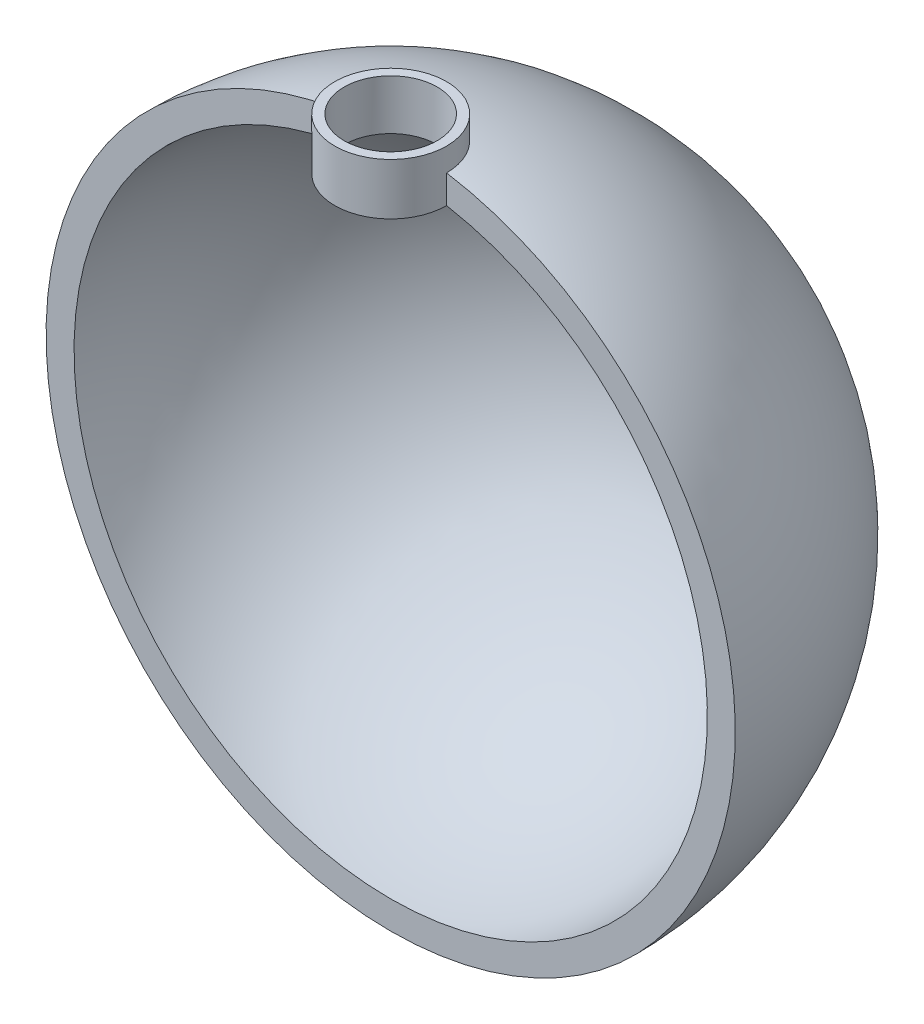
SolidWorks part; units mm, degrees
ref_plane "Front Plane" through (0, 0, 0) normal (0, 0, 1) x (1, 0, 0)
ref_plane "Top Plane" through (0, 0, 0) normal (0, 1, 0) x (1, 0, 0)
ref_plane "Right Plane" through (0, 0, 0) normal (1, 0, 0) x (0, 0, -1)
sketch "Sketch1" plane through (0, 0, 0) normal (0, 0, 1) x (1, 0, 0)
  line L0 (0, 0) -> (0, 185)
  line L1 (0, 185) -> (0, -185)
  arc A0 (0, -170) -> (0, 170) centre (0, 0) ccw
  arc A1 (0, -185) -> (0, 185) centre (0, 0) ccw
revolve "Revolve1" add sketch "Sketch1" angle 180 about L0 region at (4.1367, 177.5, 0)
sketch "Sketch3" plane through (0, 0, 0) normal (0, 1, 0) x (1, 0, 0)
  circle A0 centre (0, 0) radius 30
extrude "Boss-Extrude2" add sketch "Sketch3" along normal blind 195
sketch "Sketch7" plane through (0, 195, 0) normal (0, 1, 0) x (1, 0, 0)
  circle A0 centre (0, 0) radius 25
extrude "Cut-Extrude3" cut sketch "Sketch7" against normal up to surface (195 mm away) up to face at (0, 0, 30)
sketch "Sketch8" plane through (0, 0, 0) normal (0, 0, 1) x (1, 0, 0)
  line L0 (0, 0) -> (0, 170) construction
  line L1 (0, 0) -> (0, 170)
  line L2 (0, 170) -> (0, -170)
  arc A0 (0, -170) -> (0, 170) centre (0, 0) ccw
revolve "Cut-Revolve3" cut sketch "Sketch8" angle 180 about L0 region at (72.1502, 0, 0)
sketch "Sketch10" plane through (0, 0, 0) normal (0, 0, 1) x (1, 0, 0)
  line L0 (0, 0) -> (30, 0)
  line L1 (30, 0) -> (30, 167.332)
  line L2 (0, 0) -> (0, 170)
  line L3 (0, 0) -> (0, 213.6727) construction
  arc A0 (30, 167.332) -> (0, 170) centre (0, 0) ccw
revolve "Cut-Revolve4" cut sketch "Sketch10" angle 360 about L3
